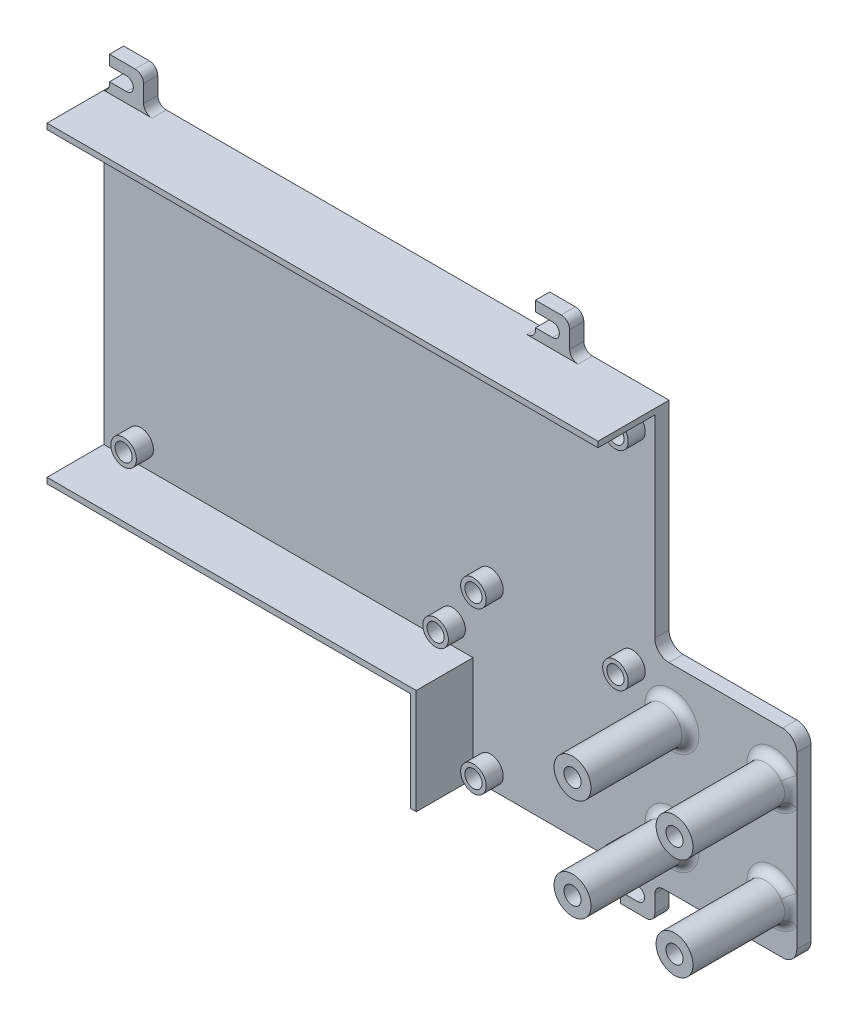
SolidWorks part; units mm, degrees
material "Custom Plastic"
ref_plane "X-Y Datum" through (0, 0, 0) normal (0, 0, 1) x (1, 0, 0)
ref_plane "X-Z Datum" through (0, 0, 0) normal (0, 1, 0) x (1, 0, 0)
ref_plane "Y-Z Datum" through (0, 0, 0) normal (1, 0, 0) x (0, 0, -1)
sketch "Sketch1" plane through (0, 0, 0) normal (0, 0, 1) x (1, 0, 0)
  line L1 (-167.3248, 270.3744) -> (-39.3248, 270.3744)
  line L2 (-167.3248, 270.3744) -> (-167.3248, 160.3744)
  line L3 (-167.3248, 160.3744) -> (-39.3248, 160.3744)
  line L4 (-39.3248, 270.3744) -> (-39.3248, 160.3744)
  line L5 (-39.3248, 270.3744) -> (26.6752, 270.3744)
  line L6 (-39.3248, 270.3744) -> (-39.3248, 125.3744)
  line L7 (-39.3248, 125.3744) -> (26.6752, 125.3744)
  line L8 (26.6752, 270.3744) -> (26.6752, 125.3744)
  line L9 (26.6752, 125.3744) -> (76.6752, 125.3744)
  line L10 (26.6752, 125.3744) -> (26.6752, 195.3744)
  line L11 (26.6752, 195.3744) -> (76.6752, 195.3744)
  line L12 (76.6752, 125.3744) -> (76.6752, 195.3744)
  dimension "D1" = 110
  dimension "D2" = 128
  dimension "D3" = 66
  dimension "D4" = 145
  dimension "D5" = 50
  dimension "D6" = 70
extrude "Boss-Extrude1" add sketch "Sketch1" along normal blind 5 contours L4 L1 L2 L3 | L8 L5 L4 L6 L7 | L9 L12 L11 L8 region at (-103.3248, 215.3744, 0) region at (-6.3248, 197.8744, 0) region at (51.6752, 160.3744, 0)
sketch "Sketch2" plane through (0, 0, 5) normal (0, 0, 1) x (1, 0, 0)
  circle A0 centre (-44.4998, 262.4914) radius 3.025
  circle A1 centre (-154.3548, 262.4914) radius 3.025
  circle A2 centre (-154.3548, 262.4914) radius 4.5
  circle A3 centre (-44.4998, 262.4914) radius 4.5
  circle A4 centre (-44.4998, 169.5274) radius 3.025
  circle A5 centre (-44.4998, 169.5274) radius 4.5
  circle A6 centre (-154.3548, 169.5274) radius 4.5
  circle A7 centre (-154.3548, 169.5274) radius 3.025
  circle A8 centre (-31.1818, 131.5554) radius 4.5
  circle A9 centre (-31.1818, 131.5554) radius 3.025
  circle A10 centre (18.8182, 131.5554) radius 3.025
  circle A11 centre (18.8182, 131.5554) radius 4.5
  circle A12 centre (18.8182, 188.3054) radius 3.025
  circle A13 centre (18.8182, 188.3054) radius 4.5
  circle A14 centre (-31.1818, 188.3054) radius 4.5
  circle A15 centre (-31.1818, 188.3054) radius 3.025
  circle A16 centre (-31.1818, 261.5554) radius 3.025
  circle A17 centre (-31.1818, 261.5554) radius 4.5
  circle A18 centre (18.8182, 261.5554) radius 4.5
  circle A19 centre (18.8182, 261.5554) radius 3.025
  point P0 (-154.3548, 262.4914)
  point P1 (-44.4998, 262.4914)
  point P3 (-44.4998, 169.5274)
  point P5 (-154.3548, 169.5274)
  point P7 (18.8182, 261.5554)
  point P9 (-31.1818, 261.5554)
  point P11 (-31.1818, 188.3054)
  point P13 (-31.1818, 131.5554)
  point P15 (18.8182, 131.5554)
  point P17 (18.8182, 188.3054)
  dimension "D1" = 6.05
  dimension "D2" = 9
extrude "Boss-Extrude2" add sketch "Sketch2" along normal blind 6
sketch "Sketch3" plane through (0, 0, 5) normal (0, 0, 1) x (1, 0, 0)
  line L0 (26.6752, 270.3744) -> (26.6752, 195.3744) construction
  line L1 (-167.3248, 270.3744) -> (26.6752, 270.3744)
  line L2 (-167.3248, 270.3744) -> (-167.3248, 268.3744)
  line L3 (-167.3248, 268.3744) -> (26.6752, 268.3744)
  line L4 (26.6752, 270.3744) -> (26.6752, 268.3744)
  line L6 (-167.3248, 160.3744) -> (-39.3248, 160.3744)
  line L7 (-167.3248, 160.3744) -> (-167.3248, 162.3744)
  line L8 (-167.3248, 162.3744) -> (-39.3248, 162.3744)
  line L9 (-39.3248, 160.3744) -> (-39.3248, 162.3744)
  line L10 (-39.3248, 125.3744) -> (-37.3248, 125.3744)
  line L11 (-39.3248, 125.3744) -> (-39.3248, 162.3744)
  line L12 (-39.3248, 162.3744) -> (-37.3248, 162.3744)
  line L13 (-37.3248, 125.3744) -> (-37.3248, 162.3744)
  line M14 (-167.3248, 160.3744) -> (-39.3248, 160.3744)
  line M15 (-39.3248, 160.3744) -> (-39.3248, 125.3744)
  line M16 (-39.3248, 125.3744) -> (76.6752, 125.3744)
  line M19 (26.6752, 195.3744) -> (26.6752, 270.3744)
  line M20 (26.6752, 270.3744) -> (-167.3248, 270.3744)
  line M21 (-167.3248, 270.3744) -> (-167.3248, 160.3744)
  dimension "D1" = 2
  dimension "D2" = 2
  dimension "D3" = 2
extrude "Boss-Extrude3" add sketch "Sketch3" along normal blind 20 contours L13 L12 L9 M16 M15 | L9 L8 M14 M21 | L3 M21 M19 M20 region at (-103.3248, 161.3744, 5) region at (-70.3248, 269.3744, 5) region at (-38.3248, 143.8744, 5)
sketch "Sketch5" plane through (0, 0, 5) normal (0, 0, 1) x (1, 0, 0)
  circle A0 centre (32.6993, 178.3575) radius 3.025
  circle A1 centre (68.6203, 178.3575) radius 3.025
  circle A2 centre (68.6203, 142.4365) radius 3.025
  circle A3 centre (32.6993, 142.4365) radius 3.025
  circle A4 centre (68.6203, 178.3575) radius 6.5
  circle A5 centre (32.6993, 178.3575) radius 6.5
  circle A6 centre (32.6993, 142.4365) radius 6.5
  circle A7 centre (68.6203, 142.4365) radius 6.5
  point P0 (68.6203, 178.3575)
  point P1 (32.6993, 178.3575)
  point P3 (32.6993, 142.4365)
  point P5 (0, 0)
  point P20 (0, 0)
  point P21 (0, 0)
  point P22 (0, 0)
  dimension "D1" = 6.05
  dimension "D2" = 13
extrude "Boss-Extrude4" add sketch "Sketch5" along normal blind 35
fillet "Fillet1" radius 3 4 edges at (39.1993, 178.3575, 5) (75.1203, 178.3575, 5) (75.1203, 142.4365, 5) (39.1993, 142.4365, 5)
sketch "Sketch6" plane through (0, 0, 0) normal (0, 0, -1) x (-1, 0, 0)
  line L0 (167.3248, 160.3744) -> (39.3248, 160.3744) construction
  line L1 (102.3248, 160.3744) -> (90.3248, 160.3744)
  line L2 (102.3248, 160.3744) -> (102.3248, 148.3744)
  line L3 (102.3248, 148.3744) -> (90.3248, 148.3744)
  line L4 (90.3248, 160.3744) -> (90.3248, 148.3744)
  line L5 (-26.6752, 270.3744) -> (167.3248, 270.3744) construction
  line L6 (165.3248, 270.3744) -> (153.3248, 270.3744)
  line L7 (165.3248, 270.3744) -> (165.3248, 282.3744)
  line L8 (165.3248, 282.3744) -> (153.3248, 282.3744)
  line L9 (153.3248, 270.3744) -> (153.3248, 282.3744)
  line L10 (37.3248, 125.3744) -> (-76.6752, 125.3744) construction
  line L11 (-14.6752, 125.3744) -> (-26.6752, 125.3744)
  line L12 (-14.6752, 125.3744) -> (-14.6752, 113.3744)
  line L13 (-14.6752, 113.3744) -> (-26.6752, 113.3744)
  line L14 (-26.6752, 125.3744) -> (-26.6752, 113.3744)
  line L15 (96.3248, 160.3744) -> (96.3248, 148.3744) construction
  line L16 (15.3248, 270.3744) -> (3.3248, 270.3744)
  line L17 (15.3248, 270.3744) -> (15.3248, 282.3744)
  line L18 (15.3248, 282.3744) -> (3.3248, 282.3744)
  line L19 (3.3248, 270.3744) -> (3.3248, 282.3744)
  line L20 (167.3248, 162.3744) -> (167.3248, 160.3744) construction
  line L21 (159.3248, 282.3744) -> (159.3248, 270.3744) construction
  line L22 (9.3248, 282.3744) -> (9.3248, 270.3744) construction
  line L23 (-20.6752, 125.3744) -> (-20.6752, 113.3744) construction
  line L24 (167.3248, 268.3744) -> (167.3248, 162.3744) construction
  line L27 (-26.6752, 268.3744) -> (-26.6752, 195.3744) construction
  line L28 (-76.6752, 125.3744) -> (-76.6752, 137.3997) construction
  circle A0 centre (96.3248, 154.3744) radius 2 construction
  circle A1 centre (-20.6752, 119.3744) radius 2 construction
  circle A2 centre (9.3248, 276.3744) radius 2 construction
  circle A3 centre (159.3248, 276.3744) radius 2 construction
  point P48 (165.1064, 287.8651)
  dimension "D1" = 4
  dimension "D2" = 12
  dimension "D3" = 12
  dimension "D4" = 65
  dimension "D5" = 2
  dimension "D6" = 30
  dimension "D7" = 50
extrude "Boss-Extrude5" add sketch "Sketch6" against normal blind 5
hole_wizard "M4 Clearance Hole1" positions "Sketch9" profile "Sketch8" hole size "M4" standard "ANSI Metric" end condition through all
sketch "Sketch9" plane through (0, 0, 5) normal (0, 0, 1) x (1, 0, 0)
  line L0 (-96.3248, 160.3744) -> (-96.3248, 148.3744) construction
  point P0 (-96.3248, 154.3744)
  point P4 (-159.3248, 276.3744)
  point P7 (-9.3248, 276.3744)
  point P10 (20.6752, 119.3744)
sketch "Sketch8" plane through (-96.3248, 154.3744, 5) normal (1, 0, 0) x (0, -1, 0)
  line L0 (0, 0) -> (0, 5)
  line L1 (0, 5) -> (2.4, 5)
  line L2 (2.4, 5) -> (2.4, 0)
  line L5 (2.4, 0) -> (0, 0)
  line L11 (0, -6.35) -> (0, 107.95) construction
  dimension "Thru Hole Dia." = 4.8
  dimension "Thru Hole Depth" = 5
sketch "Sketch10" plane through (0, 0, 5) normal (0, 0, 1) x (1, 0, 0)
  line L0 (-159.3248, 278.7744) -> (-165.3248, 278.7744)
  line L1 (-159.3248, 282.3744) -> (-159.3248, 270.3744) construction
  line L2 (-165.3248, 270.3744) -> (-165.3248, 282.3744) construction
  line L3 (-159.3248, 273.9744) -> (-165.3248, 273.9744)
  line L4 (-96.3248, 156.7744) -> (-102.3248, 156.7744)
  line L5 (-96.3248, 160.3744) -> (-96.3248, 148.3744) construction
  line L6 (-102.3248, 160.3744) -> (-102.3248, 148.3744) construction
  line L7 (-96.3248, 151.9744) -> (-102.3248, 151.9744)
  line L8 (20.6752, 121.7744) -> (14.6752, 121.7744)
  line L9 (20.6752, 125.3744) -> (20.6752, 113.3744) construction
  line L10 (14.6752, 125.3744) -> (14.6752, 113.3744) construction
  line L11 (20.6752, 116.9744) -> (14.6752, 116.9744)
  line L12 (-9.3248, 278.7744) -> (-15.3248, 278.7744)
  line L13 (-9.3248, 282.3744) -> (-9.3248, 270.3744) construction
  line L14 (-15.3248, 270.3744) -> (-15.3248, 282.3744) construction
  line L15 (-9.3248, 273.9744) -> (-15.3248, 273.9744)
  line L20 (-102.3248, 160.3744) -> (-102.3248, 148.3744)
  line L21 (-102.3248, 148.3744) -> (-90.3248, 148.3744)
  line L22 (-90.3248, 148.3744) -> (-90.3248, 160.3744)
  line L23 (-90.3248, 160.3744) -> (-102.3248, 160.3744)
  line L24 (-102.3248, 160.3744) -> (-102.3248, 148.3744)
  line L25 (-102.3248, 148.3744) -> (-90.3248, 148.3744)
  line L26 (-90.3248, 148.3744) -> (-90.3248, 160.3744)
  line L27 (-90.3248, 160.3744) -> (-102.3248, 160.3744)
  line L28 (-15.3248, 282.3744) -> (-15.3248, 270.3744)
  line L29 (-15.3248, 270.3744) -> (-3.3248, 270.3744)
  line L30 (76.6752, 147.4732) -> (76.6752, 173.3208)
  line L31 (76.6752, 183.3942) -> (76.6752, 195.3744)
  line L32 (76.6752, 195.3744) -> (26.6752, 195.3744)
  line L33 (26.6752, 195.3744) -> (26.6752, 268.3744)
  line L34 (26.6752, 268.3744) -> (-167.3248, 268.3744)
  line L35 (-167.3248, 268.3744) -> (-167.3248, 162.3744)
  line L36 (-167.3248, 162.3744) -> (-37.3248, 162.3744)
  line L37 (-37.3248, 162.3744) -> (-37.3248, 125.3744)
  line L38 (-37.3248, 125.3744) -> (14.6752, 125.3744)
  line L39 (14.6752, 125.3744) -> (14.6752, 113.3744)
  line L40 (14.6752, 113.3744) -> (26.6752, 113.3744)
  line L41 (26.6752, 113.3744) -> (26.6752, 125.3744)
  line L44 (76.6752, 147.4732) -> (76.6752, 173.3208)
  line L45 (76.6752, 183.3942) -> (76.6752, 195.3744)
  line L46 (76.6752, 195.3744) -> (26.6752, 195.3744)
  line L47 (26.6752, 195.3744) -> (26.6752, 268.3744)
  line L48 (26.6752, 268.3744) -> (-167.3248, 268.3744)
  line L49 (-167.3248, 268.3744) -> (-167.3248, 162.3744)
  line L50 (-167.3248, 162.3744) -> (-37.3248, 162.3744)
  line L51 (-37.3248, 162.3744) -> (-37.3248, 125.3744)
  line L52 (-37.3248, 125.3744) -> (14.6752, 125.3744)
  line L53 (14.6752, 125.3744) -> (14.6752, 113.3744)
  line L54 (14.6752, 113.3744) -> (26.6752, 113.3744)
  line L55 (26.6752, 113.3744) -> (26.6752, 125.3744)
  line L58 (-3.3248, 270.3744) -> (-3.3248, 282.3744)
  line L59 (-3.3248, 282.3744) -> (-15.3248, 282.3744)
  line L60 (-15.3248, 282.3744) -> (-15.3248, 270.3744)
  line L61 (-15.3248, 270.3744) -> (-3.3248, 270.3744)
  line L62 (-3.3248, 270.3744) -> (-3.3248, 282.3744)
  line L63 (-3.3248, 282.3744) -> (-15.3248, 282.3744)
  line L64 (-165.3248, 282.3744) -> (-165.3248, 270.3744)
  line L65 (-165.3248, 270.3744) -> (-153.3248, 270.3744)
  line L66 (-153.3248, 270.3744) -> (-153.3248, 282.3744)
  line L67 (-153.3248, 282.3744) -> (-165.3248, 282.3744)
  line L68 (-165.3248, 282.3744) -> (-165.3248, 270.3744)
  line L69 (-165.3248, 270.3744) -> (-153.3248, 270.3744)
  line L70 (-153.3248, 270.3744) -> (-153.3248, 282.3744)
  line L71 (-153.3248, 282.3744) -> (-165.3248, 282.3744)
  line L80 (26.6752, 125.3744) -> (76.6752, 125.3744)
  line L81 (26.6752, 125.3744) -> (76.6752, 125.3744)
  line L82 (76.6752, 125.3744) -> (76.6752, 137.3997)
  line L83 (76.6752, 125.3744) -> (76.6752, 137.3997)
  circle A0 centre (-159.3248, 276.3744) radius 2.4 construction
  circle A1 centre (-96.3248, 154.3744) radius 2.4 construction
  circle A2 centre (20.6752, 119.3744) radius 2.4 construction
  circle A3 centre (-9.3248, 276.3744) radius 2.4 construction
  circle A4 centre (-159.3248, 276.3744) radius 2.4
  circle A5 centre (-9.3248, 276.3744) radius 2.4
  arc A6 (76.6752, 183.3942) -> (76.6752, 173.3208) centre (68.6203, 178.3575) ccw
  arc A7 (76.6752, 147.4732) -> (76.6752, 137.3997) centre (68.6203, 142.4365) ccw
  arc A8 (76.6752, 183.3942) -> (76.6752, 173.3208) centre (68.6203, 178.3575) ccw
  arc A9 (76.6752, 147.4732) -> (76.6752, 137.3997) centre (68.6203, 142.4365) ccw
  circle A10 centre (20.6752, 119.3744) radius 2.4
  circle A11 centre (-96.3248, 154.3744) radius 2.4
  circle M29 centre (-96.3248, 154.3744) radius 2.4
  line M30 (-102.3248, 160.3744) -> (-102.3248, 148.3744)
  dimension "D1" = 0
  dimension "D2" = 0
  dimension "D3" = 0
  dimension "D4" = 0
extrude "Cut-Extrude1" cut sketch "Sketch10" against normal through all contours L7 L4 M29 M30 | A4 L0 L68 L3 | A5 L12 L60 L15 | A10 L8 L53 L11 region at (-163.2324, 276.3744, 5) region at (-100.2324, 154.3744, 5) region at (16.7676, 119.3744, 5) region at (-13.2324, 276.3744, 5)
fillet "Fillet2" radius 3 12 edges at (-153.3248, 282.3744, 2.5) (-153.3248, 270.3744, 2.5) (-165.3248, 270.3744, 2.5) (-15.3248, 270.3744, 2.5) (-3.3248, 270.3744, 2.5) (-3.3248, 282.3744, 2.5) (-90.3248, 148.3744, 2.5) (26.6752, 113.3744, 2.5) (26.6752, 125.3744, 2.5) (14.6752, 125.3744, 2.5) (-102.3248, 160.3744, 2.5) (-90.3248, 160.3744, 2.5)
fillet "Fillet3" radius 5 3 edges at (26.6752, 195.3744, 2.5) (76.6752, 195.3744, 2.5) (76.6752, 125.3744, 2.5)
equation "\"16mmm\"=20"
